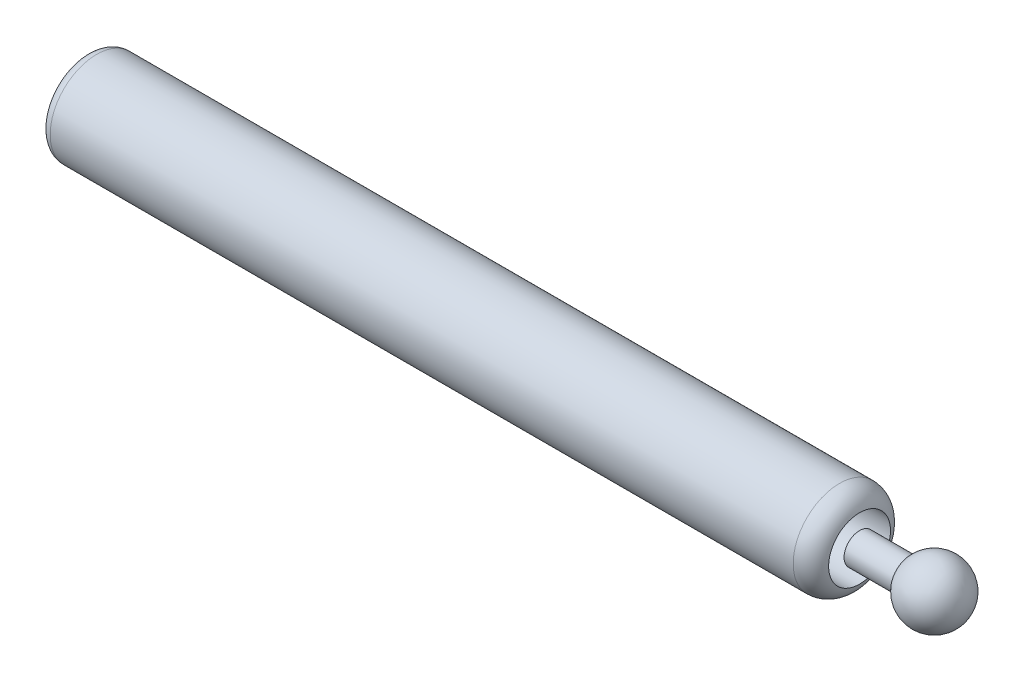
SolidWorks part; units mm, degrees
ref_plane "Front Plane" through (0, 0, 0) normal (0, 0, 1) x (1, 0, 0)
ref_plane "Top Plane" through (0, 0, 0) normal (0, 1, 0) x (1, 0, 0)
ref_plane "Right Plane" through (0, 0, 0) normal (1, 0, 0) x (0, 0, -1)
sketch "Sketch2" plane through (0, 0, 0) normal (1, 0, 0) x (0, 0, -1)
  circle A0 centre (0, 0) radius 4.5
extrude "Boss-Extrude1" add sketch "Sketch2" along normal blind 75
sketch "Sketch3" plane through (0, 0, 0) normal (-1, 0, 0) x (0, 0, 1)
  circle A0 centre (0, 0) radius 3
extrude "Cut-Extrude1" cut sketch "Sketch3" against normal blind 100
sketch "Sketch4" plane through (75, 0, 0) normal (1, 0, 0) x (0, 0, -1)
  circle A0 centre (0, 0) radius 1.5
extrude "Boss-Extrude2" add sketch "Sketch4" along normal blind 5
fillet "Fillet1" radius 2 1 edges at (75, 0, -4.5)
fillet "Fillet3" radius 1 1 edges at (0, 0, -4.5)
sketch "Sketch5" plane through (0, 0, 0) normal (0, 1, 0) x (1, 0, 0)
  line L0 (80, 0) -> (82.25, 0)
  line L2 (80, -1.5) -> (80, 1.5) construction
  line L4 (80, 0) -> (79.5, 0)
  line L5 (82.25, 0) -> (85.25, 0)
  line L6 (79.5, 0) -> (79.25, 0)
  arc A2 (85.25, 0) -> (79.25, 0) centre (82.25, 0) ccw
  dimension "D2" = 6
  dimension "D1" = 2.25
revolve "Revolve1" add sketch "Sketch5" angle 360 about L5
